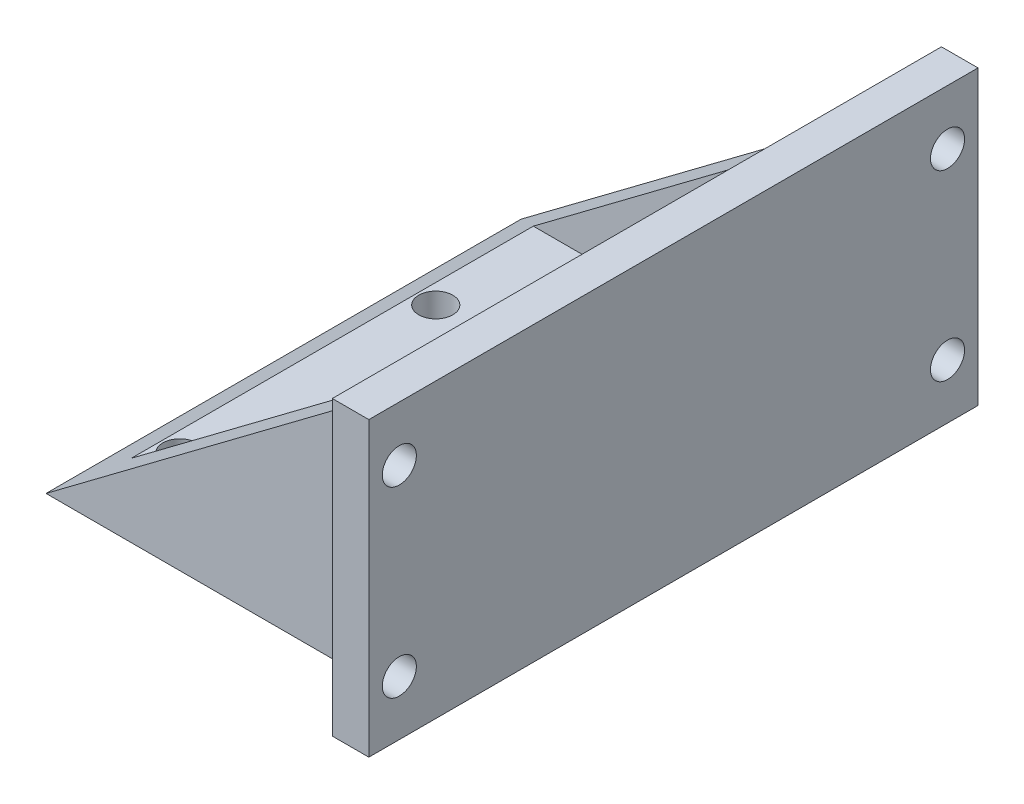
SolidWorks part; units mm, degrees
ref_plane "正面" through (0, 0, 0) normal (0, 0, 1) x (1, 0, 0)
ref_plane "平面" through (0, 0, 0) normal (0, 1, 0) x (1, 0, 0)
ref_plane "右側面" through (0, 0, 0) normal (1, 0, 0) x (0, 0, -1)
sketch "ｽｹｯﾁ1" plane through (0, 0, 0) normal (0, 0, 1) x (1, 0, 0)
  line L0 (0, 0) -> (32, 0)
  line L1 (32, 0) -> (32, 24)
  line L2 (32, 24) -> (0, 0)
  dimension "D1" = 32
  dimension "D2" = 24
extrude "ﾎﾞｽ - 押し出し1" add sketch "ｽｹｯﾁ1" along normal blind 39
shell "ｼｪﾙ1" thickness 3 removed face at (16, 12, 19.5)
sketch "ｽｹｯﾁ2" plane through (0, 0, 0) normal (0, -1, 0) x (1, 0, 0)
  line L0 (4, 36) -> (29, 36) construction
  line L1 (26.6, 33.609) -> (5.6, 33.609) construction
  line L2 (26.6, 33.609) -> (26.6, 12.609) construction
  line L3 (26.6, 12.609) -> (5.6, 12.609) construction
  line L4 (5.6, 33.609) -> (5.6, 12.609) construction
  line L5 (26.6, 33.609) -> (5.6, 12.609) construction
  line L6 (26.6, 12.609) -> (5.6, 33.609) construction
  line L7 (29, 36) -> (29, 3) construction
  circle A0 centre (26.6, 12.609) radius 1.4
  circle A1 centre (5.6, 12.609) radius 1.4
  circle A2 centre (5.6, 33.609) radius 1.4
  circle A3 centre (26.6, 33.609) radius 1.4
  point P0 (16.1, 23.109)
  dimension "D1" = 2.8
  dimension "D2" = 21
  dimension "D3" = 21
  dimension "D4" = 2.4
  dimension "D5" = 2.391
extrude "ｶｯﾄ - 押し出し1" cut sketch "ｽｹｯﾁ2" against normal blind 30
sketch "ｽｹｯﾁ3" plane through (0, 0, 0) normal (0, -1, 0) x (1, 0, 0)
  circle A0 centre (16.1, 12.609) radius 6.5
  circle A2 centre (26.6, 33.609) radius 1.4
  circle A3 centre (26.6, 33.609) radius 1.4
  circle A4 centre (5.6, 33.609) radius 1.4
  circle A5 centre (5.6, 33.609) radius 1.4
  circle A6 centre (5.6, 12.609) radius 1.4
  circle A7 centre (5.6, 12.609) radius 1.4
  circle A8 centre (26.6, 12.609) radius 1.4
  circle A9 centre (26.6, 12.609) radius 1.4
  dimension "D5" = 13
  dimension "D6" = 10.5
  dimension "D1" = 0
  dimension "D2" = 0
  dimension "D3" = 0
  dimension "D4" = 0
extrude "ｶｯﾄ - 押し出し2" cut sketch "ｽｹｯﾁ3" against normal blind 5 contours A0
sketch "ｽｹｯﾁ5" plane through (32, 0, 0) normal (1, 0, 0) x (0, 0, -1)
  line L0 (-39, 24) -> (0, 24) construction
  line L13 (-44.5, 24) -> (5.5, 24)
  line L14 (-44.5, 24) -> (-44.5, 0)
  line L15 (-44.5, 0) -> (5.5, 0)
  line L16 (5.5, 24) -> (5.5, 0)
  line L17 (-39, 0) -> (0, 0) construction
  line L18 (-39, 0) -> (-39, 24) construction
  line L19 (0, 0) -> (0, 24) construction
  dimension "D1" = 5.5
  dimension "D2" = 5.5
extrude "ﾎﾞｽ - 押し出し2" add sketch "ｽｹｯﾁ5" against normal blind 3
sketch "ｽｹｯﾁ4" plane through (32, 0, 0) normal (1, 0, 0) x (0, 0, -1)
  line L0 (-39, 24) -> (0, 24) construction
  line L1 (3, 19.5) -> (-42, 19.5) construction
  line L2 (3, 19.5) -> (3, 4.5) construction
  line L3 (3, 4.5) -> (-42, 4.5) construction
  line L4 (-42, 19.5) -> (-42, 4.5) construction
  line L5 (3, 19.5) -> (-42, 4.5) construction
  line L6 (3, 4.5) -> (-42, 19.5) construction
  line L8 (5.5, 0) -> (5.5, 24) construction
  circle A0 centre (3, 19.5) radius 1.4
  circle A1 centre (-42, 19.5) radius 1.4
  circle A2 centre (-42, 4.5) radius 1.4
  circle A3 centre (3, 4.5) radius 1.4
  point P0 (-19.5, 12)
  dimension "D1" = 2.8
  dimension "D2" = 45
  dimension "D3" = 15
  dimension "D4" = 12
  dimension "D5" = 25
extrude "ｶｯﾄ - 押し出し3" cut sketch "ｽｹｯﾁ4" against normal blind 5
fillet "ﾌｨﾚｯﾄ1" radius 5 2 edges at (29, 10.875, 0) (29, 10.875, 39)
sketch "ｽｹｯﾁ6" plane through (29, 0, 0) normal (-1, 0, 0) x (0, 0, 1)
  circle A0 centre (42, 19.5) radius 2.75
  circle A1 centre (42, 4.5) radius 2.75
  circle A2 centre (-3, 19.5) radius 2.75
  circle A3 centre (-3, 4.5) radius 2.75
  dimension "D1" = 5.5
extrude "ｶｯﾄ - 押し出し4" cut sketch "ｽｹｯﾁ6" against normal blind 3 and the other way through all from offset 3
equation "\"D6@ｽｹｯﾁ3\"=21/2"
